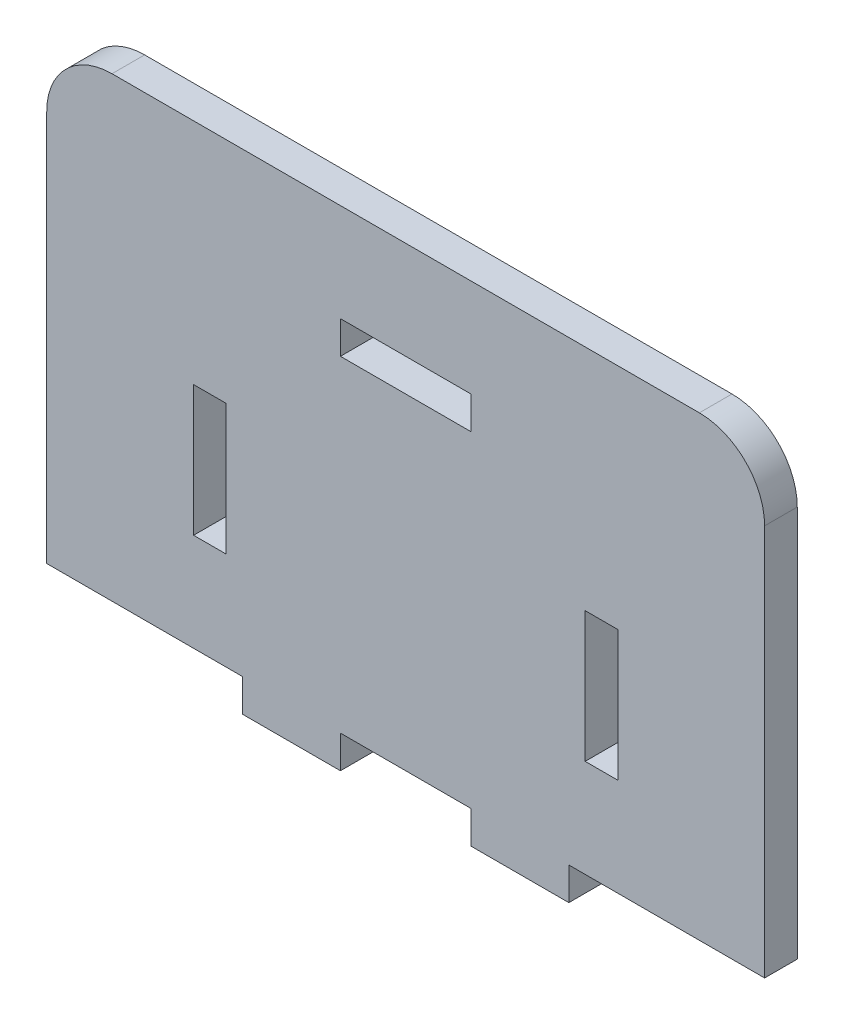
SolidWorks part; units mm, degrees
ref_plane "Plan de face" through (0, 0, 0) normal (0, 0, 1) x (1, 0, 0)
ref_plane "Plan de dessus" through (0, 0, 0) normal (0, 1, 0) x (1, 0, 0)
ref_plane "Plan de droite" through (0, 0, 0) normal (1, 0, 0) x (0, 0, -1)
sketch "Esquisse1" plane through (0, 0, 0) normal (0, 0, 1) x (1, 0, 0)
  line L0 (0, 35) -> (0, -35) construction
  line L1 (-55, 35) -> (55, 35)
  line L2 (-55, 35) -> (-55, -35)
  line L3 (-55, -35) -> (-25, -35)
  line L4 (55, 35) -> (55, -35)
  line L5 (-55, 0) -> (55, 0) construction
  line L6 (-25, -35) -> (-25, -40)
  line L7 (-25, -40) -> (-10, -40)
  line L8 (-10, -40) -> (-10, -35)
  line L9 (10, -35) -> (10, -40)
  line L10 (10, -40) -> (25, -40)
  line L11 (25, -40) -> (25, -35)
  line L12 (-10, -35) -> (10, -35)
  line L13 (25, -35) -> (55, -35)
  line L14 (-32.5, -10) -> (-27.5, -10) construction
  line L15 (-32.5, 0) -> (-27.5, 0)
  line L16 (-32.5, 0) -> (-32.5, -20)
  line L17 (-32.5, -20) -> (-27.5, -20)
  line L18 (-27.5, 0) -> (-27.5, -20)
  line L19 (27.5, 0) -> (32.5, 0)
  line L20 (27.5, 0) -> (27.5, -20)
  line L21 (27.5, -20) -> (32.5, -20)
  line L22 (32.5, 0) -> (32.5, -20)
  line L24 (-10, 20) -> (10, 20)
  line L25 (-10, 20) -> (-10, 15)
  line L26 (-10, 15) -> (10, 15)
  line L27 (10, 20) -> (10, 15)
  line L28 (-4.7305, 15) -> (-4.7305, -35) construction
  line L29 (-4.7305, -10) -> (16.2582, -10) construction
  point P8 (0, 0)
  point P11 (0, 0)
  dimension "D1" = 70
  dimension "D2" = 110
  dimension "D3" = 20
  dimension "D4" = 10
  dimension "D5" = 15
  dimension "D6" = 15
  dimension "D7" = 5
  dimension "D8" = 5
  dimension "D9" = 5
  dimension "D10" = 55
  dimension "D11" = 20
  dimension "D12" = 27.5
  dimension "D13" = 5
  dimension "D14" = 50
extrude "Boss.-Extru.1" add sketch "Esquisse1" along normal blind 5
fillet "Congé1" radius 10 2 edges at (-55, 35, 2.5) (55, 35, 2.5)
equation "\"D4@Esquisse1\"=\"D3@Esquisse1\"/2"
equation "\"D6@Esquisse1\"=\"D5@Esquisse1\""
equation "\"D8@Esquisse1\"=\"D7@Esquisse1\""
equation "\"D9@Esquisse1\"=\"D7@Esquisse1\""
equation "\"D12@Esquisse1\"=\"D10@Esquisse1\"/2"
equation "\"D13@Esquisse1\"=\"D7@Esquisse1\""
